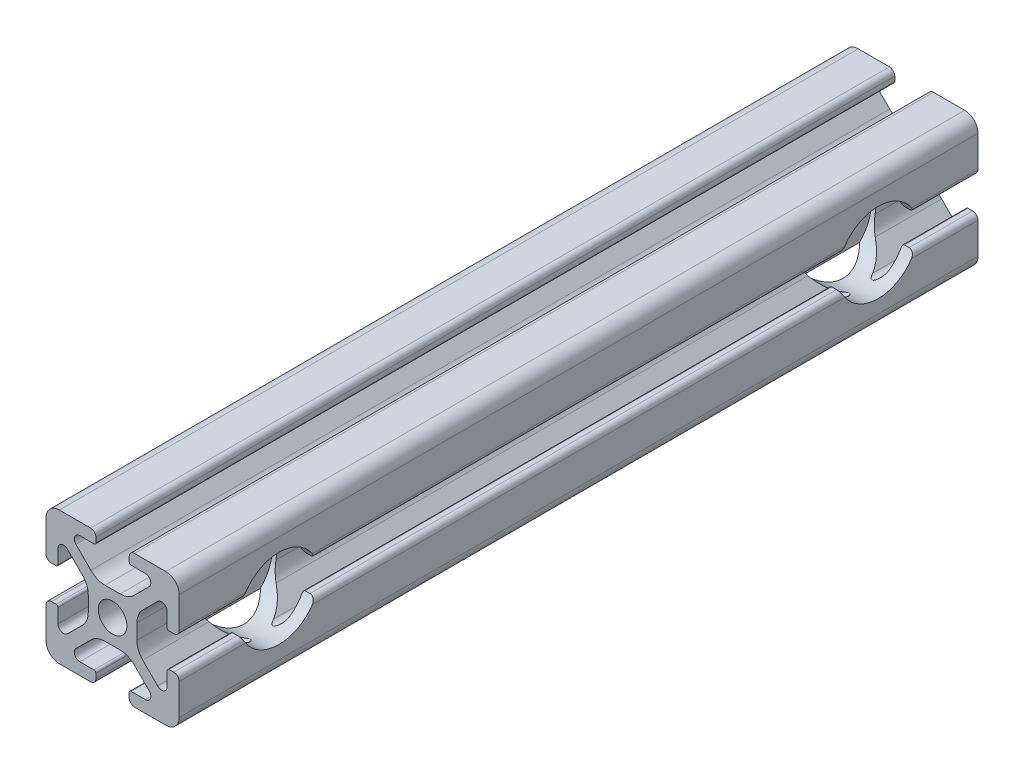
SolidWorks part; units mm, degrees
material "Alliage 1060"
ref_plane "Plan de face" through (0, 0, 0) normal (0, 0, 1) x (1, 0, 0)
ref_plane "Plan de dessus" through (0, 0, 0) normal (0, 1, 0) x (1, 0, 0)
ref_plane "Plan de droite" through (0, 0, 0) normal (1, 0, 0) x (0, 0, -1)
sketch "Esquisse1" plane through (0, 0, 0) normal (0, 0, 1) x (1, 0, 0)
  line L108 (-3.2559, 4.5287) -> (-5.5062, 6.779)
  line L109 (-4.9176, 8.2) -> (-2.8, 8.2)
  line L110 (-2.5, 8.5) -> (-2.5, 9.2)
  line L111 (-3.3, 10) -> (-8, 10)
  line L112 (-10, 8) -> (-10, 3.3)
  line L113 (-9.2, 2.5) -> (-8.5, 2.5)
  line L114 (-8.2, 2.8) -> (-8.2, 4.9176)
  line L115 (-6.779, 5.5062) -> (-4.5287, 3.2559)
  line L116 (-3.65, 1.1346) -> (-3.65, -1.1346)
  line L117 (-4.5287, -3.2559) -> (-6.779, -5.5062)
  line L118 (-8.2, -4.9176) -> (-8.2, -2.8)
  line L119 (-8.5, -2.5) -> (-9.2, -2.5)
  line L120 (-10, -3.3) -> (-10, -8)
  line L121 (-8, -10) -> (-3.3, -10)
  line L122 (-2.5, -9.2) -> (-2.5, -8.5)
  line L123 (-2.8, -8.2) -> (-4.9176, -8.2)
  line L124 (-5.5062, -6.779) -> (-3.2559, -4.5287)
  line L125 (-1.1346, -3.65) -> (1.1346, -3.65)
  line L126 (3.2559, -4.5287) -> (5.5062, -6.779)
  line L127 (4.9176, -8.2) -> (2.8, -8.2)
  line L128 (2.5, -8.5) -> (2.5, -9.2)
  line L129 (3.3, -10) -> (8, -10)
  line L130 (10, -8) -> (10, -3.3)
  line L131 (9.2, -2.5) -> (8.5, -2.5)
  line L132 (8.2, -2.8) -> (8.2, -4.9176)
  line L133 (6.779, -5.5062) -> (4.5287, -3.2559)
  line L134 (3.65, -1.1346) -> (3.65, 1.1346)
  line L135 (4.5287, 3.2559) -> (6.779, 5.5062)
  line L136 (8.2, 4.9176) -> (8.2, 2.8)
  line L137 (8.5, 2.5) -> (9.2, 2.5)
  line L138 (10, 3.3) -> (10, 8)
  line L139 (8, 10) -> (3.3, 10)
  line L140 (2.5, 9.2) -> (2.5, 8.5)
  line L141 (2.8, 8.2) -> (4.9176, 8.2)
  line L142 (5.5062, 6.779) -> (3.2559, 4.5287)
  line L143 (1.1346, 3.65) -> (-1.1346, 3.65)
  arc A42 (-2.15, 0) -> (2.15, 0) centre (0, 0) ccw
  arc A43 (2.15, 0) -> (-2.15, 0) centre (0, 0) ccw
  arc A108 (-4.9176, 8.2) -> (-5.5062, 6.779) centre (-4.9176, 7.3676) ccw
  arc A109 (-2.8, 8.2) -> (-2.5, 8.5) centre (-2.8, 8.5) ccw
  arc A110 (-2.5, 9.2) -> (-3.3, 10) centre (-3.3, 9.2) ccw
  arc A111 (-8, 10) -> (-10, 8) centre (-8, 8) ccw
  arc A112 (-10, 3.3) -> (-9.2, 2.5) centre (-9.2, 3.3) ccw
  arc A113 (-8.5, 2.5) -> (-8.2, 2.8) centre (-8.5, 2.8) ccw
  arc A114 (-6.779, 5.5062) -> (-8.2, 4.9176) centre (-7.3676, 4.9176) ccw
  arc A115 (-3.65, 1.1346) -> (-4.5287, 3.2559) centre (-6.65, 1.1346) ccw
  arc A116 (-4.5287, -3.2559) -> (-3.65, -1.1346) centre (-6.65, -1.1346) ccw
  arc A117 (-8.2, -4.9176) -> (-6.779, -5.5062) centre (-7.3676, -4.9176) ccw
  arc A118 (-8.2, -2.8) -> (-8.5, -2.5) centre (-8.5, -2.8) ccw
  arc A119 (-9.2, -2.5) -> (-10, -3.3) centre (-9.2, -3.3) ccw
  arc A120 (-10, -8) -> (-8, -10) centre (-8, -8) ccw
  arc A121 (-3.3, -10) -> (-2.5, -9.2) centre (-3.3, -9.2) ccw
  arc A122 (-2.5, -8.5) -> (-2.8, -8.2) centre (-2.8, -8.5) ccw
  arc A123 (-5.5062, -6.779) -> (-4.9176, -8.2) centre (-4.9176, -7.3676) ccw
  arc A124 (-1.1346, -3.65) -> (-3.2559, -4.5287) centre (-1.1346, -6.65) ccw
  arc A125 (3.2559, -4.5287) -> (1.1346, -3.65) centre (1.1346, -6.65) ccw
  arc A126 (4.9176, -8.2) -> (5.5062, -6.779) centre (4.9176, -7.3676) ccw
  arc A127 (2.8, -8.2) -> (2.5, -8.5) centre (2.8, -8.5) ccw
  arc A128 (2.5, -9.2) -> (3.3, -10) centre (3.3, -9.2) ccw
  arc A129 (8, -10) -> (10, -8) centre (8, -8) ccw
  arc A130 (10, -3.3) -> (9.2, -2.5) centre (9.2, -3.3) ccw
  arc A131 (8.5, -2.5) -> (8.2, -2.8) centre (8.5, -2.8) ccw
  arc A132 (6.779, -5.5062) -> (8.2, -4.9176) centre (7.3676, -4.9176) ccw
  arc A133 (3.65, -1.1346) -> (4.5287, -3.2559) centre (6.65, -1.1346) ccw
  arc A134 (4.5287, 3.2559) -> (3.65, 1.1346) centre (6.65, 1.1346) ccw
  arc A135 (8.2, 4.9176) -> (6.779, 5.5062) centre (7.3676, 4.9176) ccw
  arc A136 (8.2, 2.8) -> (8.5, 2.5) centre (8.5, 2.8) ccw
  arc A137 (9.2, 2.5) -> (10, 3.3) centre (9.2, 3.3) ccw
  arc A138 (10, 8) -> (8, 10) centre (8, 8) ccw
  arc A139 (3.3, 10) -> (2.5, 9.2) centre (3.3, 9.2) ccw
  arc A140 (2.5, 8.5) -> (2.8, 8.2) centre (2.8, 8.5) ccw
  arc A141 (5.5062, 6.779) -> (4.9176, 8.2) centre (4.9176, 7.3676) ccw
  arc A142 (1.1346, 3.65) -> (3.2559, 4.5287) centre (1.1346, 6.65) ccw
  arc A143 (-3.2559, 4.5287) -> (-1.1346, 3.65) centre (-1.1346, 6.65) ccw
extrude "Boss.-Extru.1" add sketch "Esquisse1" along normal blind 120
sketch "Esquisse2" plane through (10, 0, 0) normal (1, 0, 0) x (0, 0, -1)
  line L0 (-120, 8) -> (-120, -8) construction
  line L1 (0, 0) -> (-120, 0) construction
  circle A0 centre (-105, 0) radius 6
  circle A1 centre (-15, 0) radius 6
  dimension "D2" = 12
  dimension "D4" = 12
  dimension "D1" = 15
  dimension "D3" = 15
extrude "Enlèv. mat.-Extru.1" cut sketch "Esquisse2" against normal blind 7
sketch "Esquisse3" plane through (3, 0, 0) normal (1, 0, 0) x (0, 0, -1)
  circle A0 centre (-105, 0) radius 2.5
  circle A1 centre (-15, 0) radius 2.5
  arc A2 (-100.816, -4.3005) -> (-100.816, 4.3005) centre (-105, 0) ccw construction
  arc A3 (-10.816, -4.3005) -> (-10.816, 4.3005) centre (-15, 0) ccw construction
  dimension "D1" = 5
extrude "Enlèv. mat.-Extru.2" cut sketch "Esquisse3" against normal through all
equation "\"Length\"= 120"
equation "\"D1@Boss.-Extru.1\"=\"Length\""
